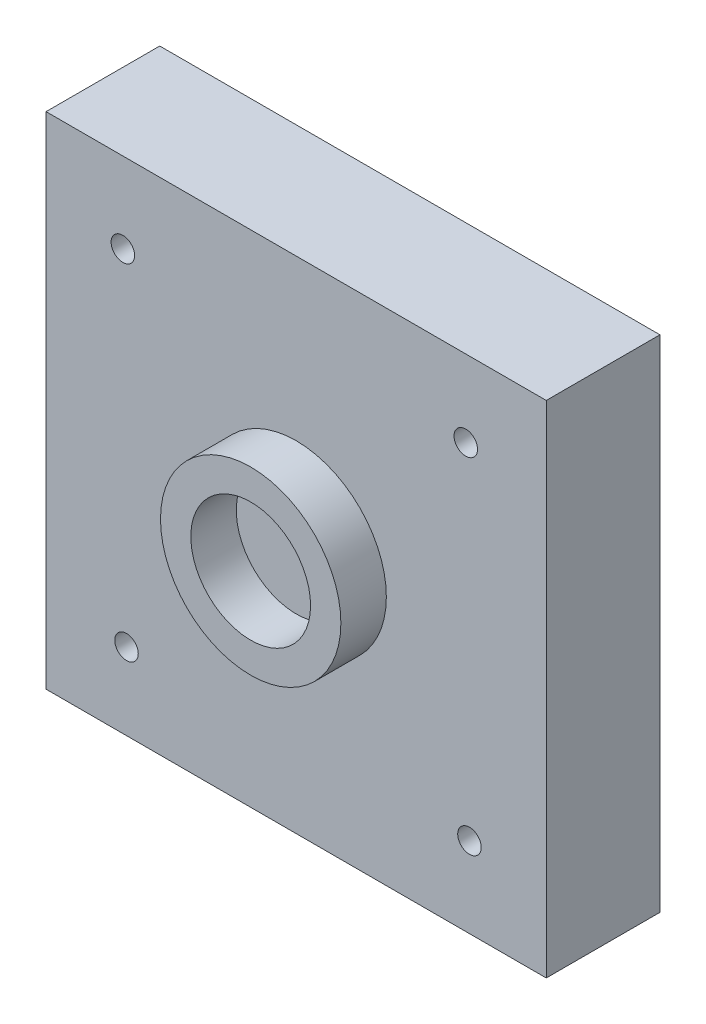
SolidWorks part; units mm, degrees
ref_plane "Front Plane" through (0, 0, 0) normal (0, 0, 1) x (1, 0, 0)
ref_plane "Top Plane" through (0, 0, 0) normal (0, 1, 0) x (1, 0, 0)
ref_plane "Right Plane" through (0, 0, 0) normal (1, 0, 0) x (0, 0, -1)
sketch "Sketch1" plane through (0, 0, 0) normal (0, 0, 1) x (1, 0, 0)
  line L0 (0, -42.5) -> (0, 0) construction
  line L1 (30, 30) -> (-30, 30)
  line L2 (30, 30) -> (30, -30)
  line L3 (30, -30) -> (-30, -30)
  line L4 (-30, 30) -> (-30, -30)
  circle A0 centre (0, 0) radius 65 construction
  dimension "D2" = 30
  dimension "D4" = 30
  dimension "D1" = 60
  dimension "D3" = 30
extrude "Extrude-Thin1" add sketch "Sketch1" along normal blind 15 thin thin type one direction wall 3
extrude "Boss-Extrude1" add sketch "Sketch1<2>" against normal blind 5 from surface starting at face at (0, 0, 15)
sketch "Sketch1<2>" plane through (0, 0, 0) normal (0, 0, 1) x (1, 0, 0) same geometry as "Sketch1"
sketch "Sketch2" plane through (0, 0, 15) normal (0, 0, 1) x (1, 0, 0)
  circle A0 centre (22.3843, 22.8679) radius 1.55
  circle A1 centre (22.8679, -22.3843) radius 1.55
  circle A2 centre (-22.3843, -22.8679) radius 1.55
  circle A3 centre (-22.8679, 22.3843) radius 1.55
  point P12 (0, 0)
  dimension "D2" = 3.1
  dimension "D1" = 32
  dimension "D3" = 4
extrude "Cut-Extrude1" cut sketch "Sketch2" against normal through all
extrude "Extrude-Thin2" add sketch "Sketch2<2>" against normal up to surface (15 mm away) thin thin type one direction wall 2
sketch "Sketch2<2>" plane through (0, 0, 15) normal (0, 0, 1) x (1, 0, 0) same geometry as "Sketch2"
sketch "Sketch3" plane through (0, 0, 15) normal (0, 0, 1) x (1, 0, 0)
  circle A0 centre (0, 0) radius 7.9
  circle A1 centre (0, 0) radius 11.9
  dimension "D1" = 4
  dimension "D2" = 15.8
extrude "Boss-Extrude2" add sketch "Sketch3" along normal blind 6
